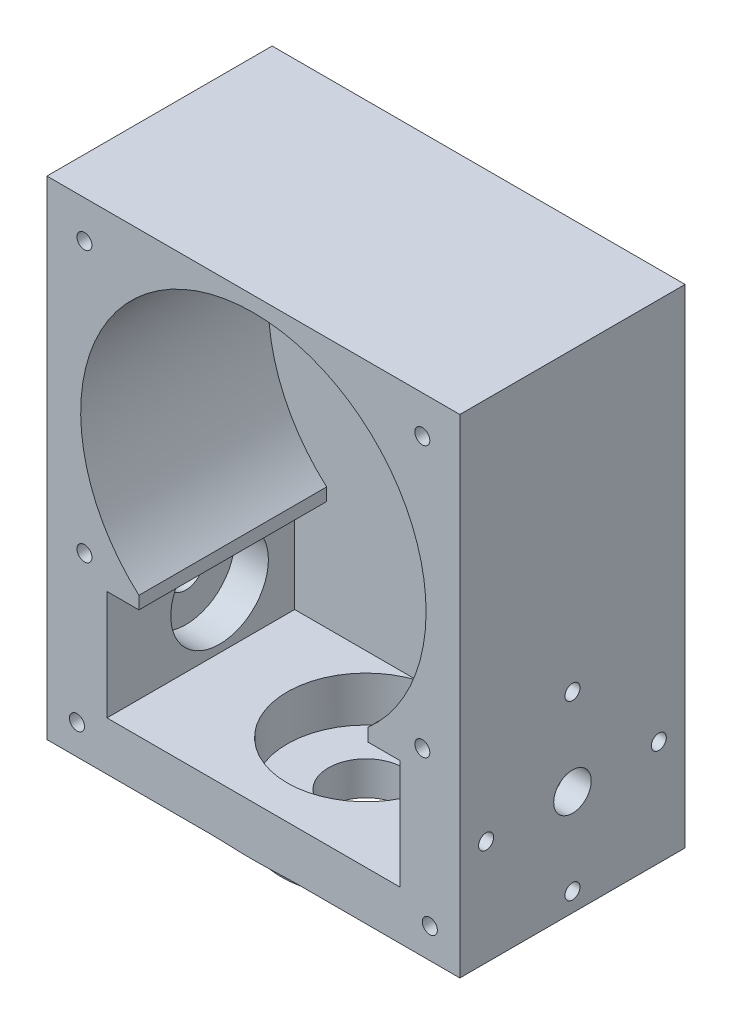
SolidWorks part; units mm, degrees
ref_plane "Front Plane" through (0, 0, 0) normal (0, 0, 1) x (1, 0, 0)
ref_plane "Top Plane" through (0, 0, 0) normal (0, 1, 0) x (1, 0, 0)
ref_plane "Right Plane" through (0, 0, 0) normal (1, 0, 0) x (0, 0, -1)
sketch "Sketch1" plane through (0, 0, 0) normal (0, 0, 1) x (1, 0, 0)
  line L1 (-55, -60) -> (55, -60)
  line L2 (-55, -60) -> (-55, 70)
  line L3 (-55, 70) -> (55, 70)
  line L4 (55, -60) -> (55, 70)
  dimension "D1" = 110
  dimension "D2" = 130
  dimension "D3" = 55
  dimension "D4" = 60
extrude "Boss-Extrude1" add sketch "Sketch1" along normal mid plane 10
sketch "Sketch6" plane through (0, 0, -5) normal (0, 0, -1) x (-1, 0, 0)
  circle A0 centre (0, 20) radius 21
  dimension "D1" = 42
  dimension "D2" = 20
sketch "Sketch9" plane through (0, 0, 0) normal (1, 0, 0) x (0, 0, -1)
  line L0 (20.8617, 20) -> (-52.2227, 20) construction
  line L1 (-52.2227, 20) -> (-52.2227, -32) construction
  dimension "D1" = 52
sketch "Sketch10" plane through (0, -60, 0) normal (0, -1, 0) x (1, 0, 0)
  line L1 (-55, -5) -> (55, -5)
  line L2 (-55, -5) -> (-55, 55)
  line L3 (-55, 55) -> (55, 55)
  line L4 (55, -5) -> (55, 55)
  dimension "D1" = 110
  dimension "D2" = 60
extrude "Boss-Extrude4" add sketch "Sketch10" against normal blind 13
extrude "Cut-Extrude2" cut sketch "Sketch6" against normal blind 30
sketch "Sketch16" plane through (0, 0, -5) normal (0, 0, -1) x (-1, 0, 0)
  circle A0 centre (0, 20) radius 27.5
  circle A3 centre (0, 20) radius 21
  circle A4 centre (0, 20) radius 21
  dimension "D1" = 55
  dimension "D2" = 0
extrude "Boss-Extrude6" add sketch "Sketch16" along normal blind 12
sketch "Sketch17" plane through (0, 0, -17) normal (0, 0, -1) x (-1, 0, 0)
  circle A2 centre (0, 20) radius 27.5
  circle A3 centre (0, 20) radius 10
  dimension "D1" = 20
extrude "Boss-Extrude7" add sketch "Sketch17" along normal blind 5
sketch "Sketch18" plane through (0, 0, 5) normal (0, 0, 1) x (1, 0, 0)
  line L0 (-55, -47) -> (-39, -47)
  line L1 (55, -47) -> (-55, -47) construction
  line L2 (-39, -47) -> (-39, -17.8222)
  line L3 (-39, -17.8222) -> (-30.4822, -17.8222)
  line L4 (0, -77.0477) -> (0, 71.7935) construction
  line L5 (55, -47) -> (39, -47)
  line L6 (39, -17.8222) -> (30.4822, -17.8222)
  line L7 (39, -47) -> (39, -17.8222)
  line L8 (-55, -47) -> (-55, 70)
  line L9 (-55, 70) -> (55, 70)
  line L10 (55, 70) -> (55, -47)
  line L11 (-30.4822, -17.8222) -> (-30.4822, -14.4505)
  line L12 (30.4822, -17.8222) -> (30.4822, -14.4505)
  arc A0 (30.4822, -14.4505) -> (-30.4822, -14.4505) centre (0, 20) ccw
  dimension "D1" = 92
  dimension "D2" = 16
  dimension "D3" = 16
extrude "Boss-Extrude8" add sketch "Sketch18" along normal blind 50
sketch "Sketch19" plane through (0, -60, 0) normal (0, -1, 0) x (1, 0, 0)
  line L1 (0, -20.8617) -> (0, 52.2227) construction
  circle A1 centre (0, 25) radius 10
  dimension "D1" = 20
  dimension "D2" = 25
extrude "Cut-Extrude3" cut sketch "Sketch19" against normal blind 50
sketch "Sketch21" plane through (0, -47, 0) normal (0, 1, 0) x (1, 0, 0)
  circle A2 centre (0, -25) radius 21
  circle A3 centre (0, -25) radius 21
  dimension "D1" = 11
extrude "Cut-Extrude4" cut sketch "Sketch21" against normal blind 12
sketch "Sketch22" plane through (0, -60, 0) normal (0, -1, 0) x (1, 0, 0)
  circle A0 centre (0, 25) radius 10
  circle A1 centre (0, 25) radius 22.5
  dimension "D1" = 45
extrude "Boss-Extrude9" add sketch "Sketch22" along normal blind 8
fillet "Fillet1" radius 10 1 edges at (0, -60, 2.5)
fillet "Fillet2" radius 10 1 edges at (-27.5, 20, -5)
fillet "Fillet3" radius 2 1 edges at (-27.5, 20, -22)
sketch "Sketch23" plane through (-39, 0, 0) normal (1, 0, 0) x (0, 0, -1)
  line L0 (-5, -47) -> (-5, -17.8222) construction
  line L2 (20.8617, 20) -> (-52.2227, 20) construction
  circle A0 centre (-25, -32) radius 13
  dimension "D2" = 26
  dimension "D1" = 20
  dimension "D3" = 52
extrude "Cut-Extrude5" cut sketch "Sketch23" against normal blind 9
sketch "Sketch24" plane through (-48, 0, 0) normal (1, 0, 0) x (0, 0, -1)
  circle A0 centre (-25, -32) radius 5
  dimension "D1" = 10
extrude "Cut-Extrude6" cut sketch "Sketch24" against normal blind 9
mirror "Mirror1" about plane through (0, 0, 0) normal (1, 0, 0) of "Cut-Extrude6", "Cut-Extrude5"
sketch "Sketch27" plane through (-55, 0, 0) normal (-1, 0, 0) x (0, 0, 1)
  line L1 (48, -32) -> (46, -32) construction
  line L3 (21.4645, -28.4645) -> (25, -32) construction
  line L4 (4, -32) -> (2, -32) construction
  circle A2 centre (2, -32) radius 2
  circle A3 centre (48, -32) radius 2
  circle A4 centre (25, -55) radius 2
  circle A5 centre (25, -9) radius 2
  dimension "D2" = 4
extrude "Cut-Extrude7" cut sketch "Sketch27" against normal blind 10
mirror "Mirror2" about plane through (0, 0, 0) normal (1, 0, 0) of "Cut-Extrude7"
sketch "Sketch28" plane through (0, 0, 55) normal (0, 0, 1) x (1, 0, 0)
  line L0 (55, 70) -> (-55, 70) construction
  line L1 (-55, 70) -> (-55, -60) construction
  line L2 (0, 70) -> (0, -60.2676) construction
  line L3 (-11.9649, -60) -> (-55, -60) construction
  circle A0 centre (-45, 60) radius 2
  circle A2 centre (-45, -12) radius 2
  circle A3 centre (-47, -52) radius 2
  circle A4 centre (47, -52) radius 2
  circle A5 centre (45, -12) radius 2
  circle A6 centre (45, 60) radius 2
  spline S0 degree 3 poles (-11.9649, -60) (-9.9708, -60) (-7.9771, -60.0792) (-4.9864, -60.1806) (-3.9895, -60.2119) (-1.9956, -60.2554) (-0.0017, -60.2798) (1.9925, -60.2555) (3.9867, -60.212) (4.9838, -60.1807) (7.9753, -60.0793) (9.9693, -60) (11.9649, -60) knots 0 0 0 0 0.25 0.25 0.375 0.375 0.5 0.625 0.625 0.75 0.75 1 1 1 1 construction
  dimension "D1" = 4
  dimension "D3" = 10
  dimension "D4" = 4
  dimension "D5" = 10
  dimension "D6" = 48
  dimension "D7" = 4
  dimension "D8" = 8
  dimension "D9" = 8
  dimension "D2" = 10
extrude "Cut-Extrude8" cut sketch "Sketch28" against normal blind 10
sketch "Sketch15" plane through (-55, 0, 0) normal (-1, 0, 0) x (0, 0, 1)
  line L0 (-20.8617, 20) -> (52.2227, 20) construction
  line L1 (0, 70) -> (0, -60) construction
  circle A0 centre (25, -32) radius 9.9855
  dimension "D1" = 52
  dimension "D2" = 25
